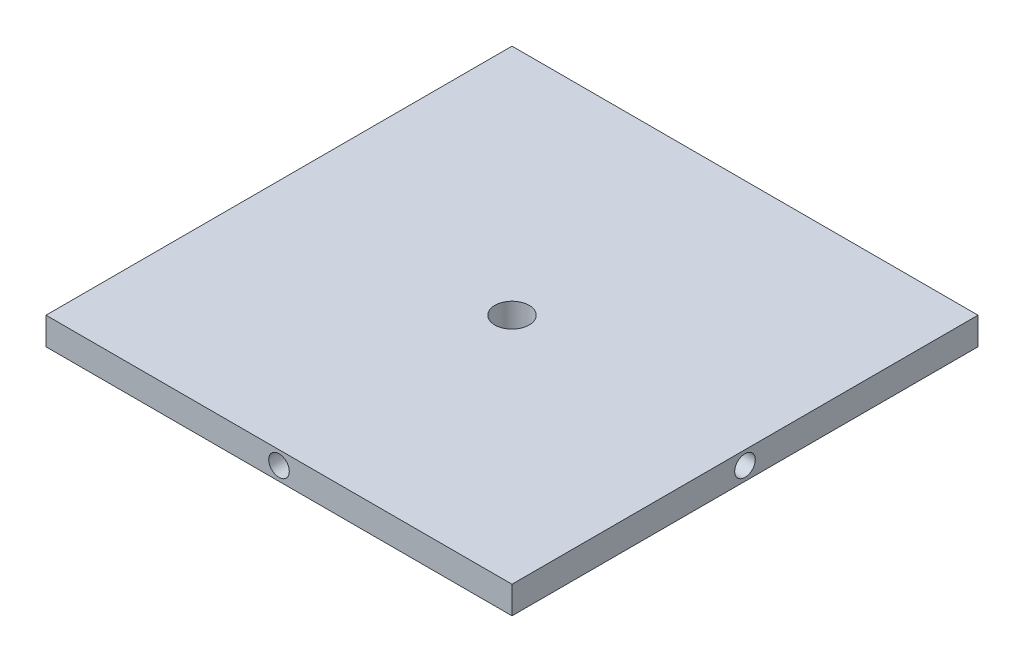
SolidWorks part; units mm, degrees
ref_plane "Front Plane" through (0, 0, 0) normal (0, 0, 1) x (1, 0, 0)
ref_plane "Top Plane" through (0, 0, 0) normal (0, 1, 0) x (1, 0, 0)
ref_plane "Right Plane" through (0, 0, 0) normal (1, 0, 0) x (0, 0, -1)
ref_plane "Plane1" through (0, 12.7, 0) normal (0, 1, 0) x (1, 0, 0)
sketch "Sketch1" plane through (0, 0, 0) normal (0, 1, 0) x (1, 0, 0)
  line L1 (-215.9, -215.9) -> (215.9, -215.9)
  line L2 (-215.9, -215.9) -> (-215.9, 215.9)
  line L3 (-215.9, 215.9) -> (215.9, 215.9)
  line L4 (215.9, -215.9) -> (215.9, 215.9)
  line L5 (-215.9, -215.9) -> (215.9, 215.9) construction
  line L6 (-215.9, 215.9) -> (215.9, -215.9) construction
  circle A0 centre (0, 0) radius 15.875
  point P0 (0, 0)
  dimension "D3" = 31.75
  dimension "D1" = 431.8
  dimension "D2" = 431.8
extrude "Boss-Extrude1" add sketch "Sketch1" along normal blind 25.4
ref_axis "Axis1" through (0, 12.7, -265.43) along (0, 0, 1)
ref_axis "Axis2" through (265.43, 12.7, 0) along (-1, 0, 0)
hole_wizard "3/4 (0.75) Diameter Hole2" positions "Sketch4" profile "Sketch5" hole size "3/4" standard "ANSI Inch"
sketch "Sketch4" plane through (215.9, 0, 0) normal (1, 0, 0) x (0, 0, -1)
  point P0 (0, 12.7)
  point P3 (0, 0)
sketch "Sketch5" plane through (215.9, 12.7, 0) normal (0, 1, 0) x (0, 0, -1)
  line L0 (0, 0) -> (0, 81.9232)
  line L1 (0, 81.9232) -> (9.525, 76.2)
  line L2 (9.525, 76.2) -> (9.525, 0)
  line L5 (9.525, 0) -> (0, 0)
  line L10 (0, 81.9232) -> (-9.525, 76.2) construction
  line L11 (0, -6.35) -> (0, 107.95) construction
  dimension "Hole Dia." = 19.05
  dimension "Hole Depth" = 76.2
  dimension "Drill Angle" = 118
hole_wizard "3/4 (0.75) Diameter Hole1" positions "Sketch2" profile "Sketch3" hole size "3/4" standard "ANSI Inch"
sketch "Sketch2" plane through (0, 0, 215.9) normal (0, 0, 1) x (1, 0, 0)
  point P0 (0, 12.7)
  point P3 (0, 0)
sketch "Sketch3" plane through (0, 12.7, 215.9) normal (1, 0, 0) x (0, -1, 0)
  line L0 (0, 0) -> (0, 81.9232)
  line L1 (0, 81.9232) -> (9.525, 76.2)
  line L2 (9.525, 76.2) -> (9.525, 0)
  line L5 (9.525, 0) -> (0, 0)
  line L10 (0, 81.9232) -> (-9.525, 76.2) construction
  line L11 (0, -6.35) -> (0, 107.95) construction
  dimension "Hole Dia." = 19.05
  dimension "Hole Depth" = 76.2
  dimension "Drill Angle" = 118
